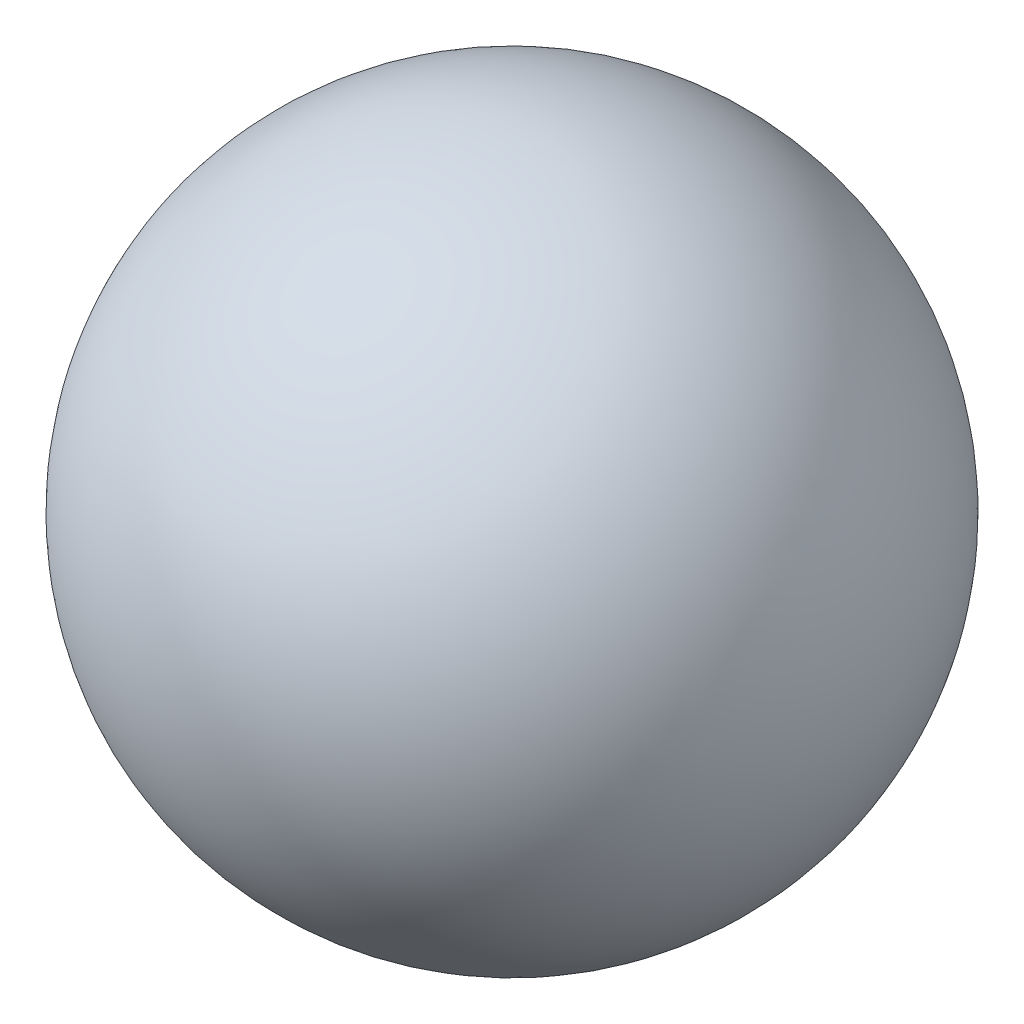
SolidWorks part; units mm, degrees
ref_plane "Front Plane" through (0, 0, 0) normal (0, 0, 1) x (1, 0, 0)
ref_plane "Top Plane" through (0, 0, 0) normal (0, 1, 0) x (1, 0, 0)
ref_plane "Right Plane" through (0, 0, 0) normal (1, 0, 0) x (0, 0, -1)
sketch "Sketch1" plane through (0, 0, 0) normal (0, 1, 0) x (1, 0, 0)
  line L0 (-39.5075, 15.2674) -> (20.4925, 15.2674)
  arc A1 (20.4925, 15.2674) -> (-39.5075, 15.2674) centre (-9.5075, 15.2674) ccw
revolve "Revolve3" add sketch "Sketch1" angle 360 about L0 region at (-9.5075, 0, -27.9998)
ref_point "center"
ref_axis "Axis1" through (-9.5075, 0, -15.2674) along (0, 1, 0)
ref_plane "Plane1" through (0, 30, 0) normal (0, 1, 0) x (1, 0, 0)
ref_plane "Plane2" through (0, -30, 0) normal (0, -1, 0) x (-1, 0, 0)
ref_point "wrist up"
ref_point "wrist down"
ref_axis "wrsit_up+right" through (-9.5075, 30, -15.2674) along (1, 0, 0)
ref_axis "wrsit_up+front" through (-9.5075, 30, -15.2674) along (0, 0, 1)
ref_axis "wrsit_dwon+right" through (-9.5075, -30, -15.2674) along (1, 0, 0)
ref_axis "wrsit_dwon+front" through (-9.5075, -30, -15.2674) along (0, 0, 1)
